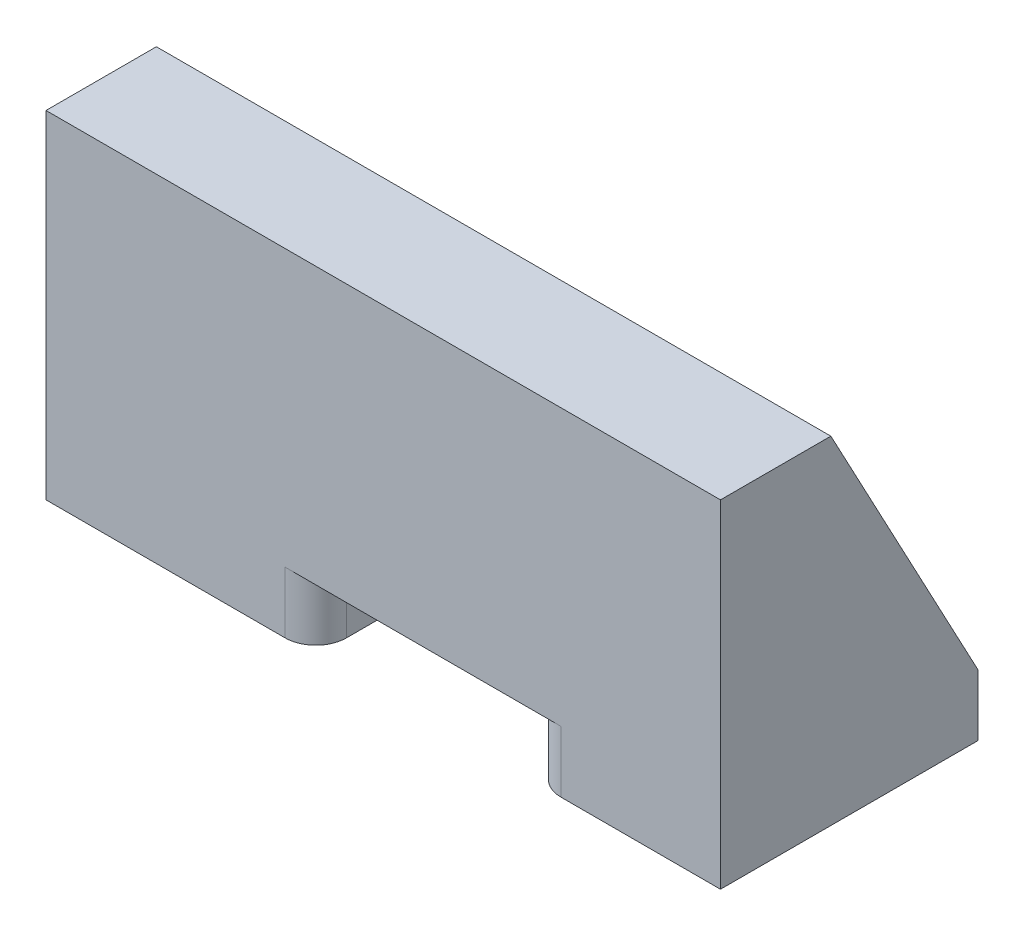
SolidWorks part; units mm, degrees
material "ABS"
ref_plane "Front" through (0, 0, 0) normal (0, 0, 1) x (1, 0, 0)
ref_plane "Top" through (0, 0, 0) normal (0, 1, 0) x (1, 0, 0)
ref_plane "Right" through (0, 0, 0) normal (1, 0, 0) x (0, 0, -1)
sketch "Sketch1" plane through (0, 0, 0) normal (0, 1, 0) x (1, 0, 0)
  line L1 (-55, -21) -> (55, -21)
  line L2 (-55, -21) -> (-55, 21)
  line L3 (-55, 21) -> (55, 21)
  line L4 (55, -21) -> (55, 21)
  line L5 (-55, -21) -> (55, 21) construction
  line L6 (-55, 21) -> (55, -21) construction
  point P0 (0, 0)
  dimension "D1" = 110
  dimension "D2" = 42
extrude "Boss-Extrude1" add sketch "Sketch1" along normal blind 10
hole_wizard "CBORE for M3 SBHCS1" positions "Sketch3" profile "Sketch2" counterbore size "M3" standard "ANSI Metric" end condition through all
sketch "Sketch3" plane through (0, 10, 0) normal (0, 1, 0) x (1, 0, 0)
  line L0 (-55, 8) -> (-45, 8) construction
  line L1 (-55, 21) -> (-55, -21) construction
  line L2 (-45, 8) -> (55, 8) construction
  line L3 (55, -21) -> (55, 21) construction
  line L5 (-55, -21) -> (55, -21) construction
  point P0 (-45, 8)
  point P2 (-32, 3)
  point P4 (32, 3)
  point P6 (45, 8)
  dimension "D1" = 90
  dimension "D2" = 29
  dimension "D3" = 13
  dimension "D4" = 5
  dimension "D5" = 13
  dimension "D6" = 5
  dimension "D7" = 10
sketch "Sketch2" plane through (-45, 10, -8) normal (1, 0, 0) x (0, 0, 1)
  line L0 (0, 0) -> (0, 10)
  line L1 (0, 10) -> (1.7, 10)
  line L3 (1.7, 10) -> (1.7, 5)
  line L4 (1.7, 5) -> (4, 5)
  line L5 (4, 5) -> (4, 0)
  line L7 (4, 0) -> (0, 0)
  line L11 (0, -6.35) -> (0, 107.95) construction
  dimension "Thru Hole Dia." = 3.4
  dimension "Thru Hole Depth" = 10
  dimension "C'Bore Dia." = 8
  dimension "C'Bore Depth" = 5
sketch "Sketch4" plane through (0, 10, 0) normal (0, 1, 0) x (1, 0, 0)
  line L3 (-55, -21) -> (55, -21) construction
  line L11 (24, -21) -> (24, 6)
  line L12 (19, 11) -> (-6, 11)
  line L13 (-11, 6) -> (-11, -21)
  line L14 (-11, -21) -> (24, -21)
  arc A0 (-6, 11) -> (-11, 6) centre (-6, 6) ccw
  arc A1 (19, 11) -> (24, 6) centre (19, 6) cw
  circle A2 centre (-32, 3) radius 1.7 construction
  point P11 (24, 11)
  dimension "D1" = 21
  dimension "D5" = 5
  dimension "D2" = 5
  dimension "D4" = 32
  dimension "D6" = 35
extrude "Cut-Extrude1" cut sketch "Sketch4" against normal up to surface (10 mm away) up to face at (-45, 0, -6.3)
fillet "Fillet2" radius 5 2 edges at (24, 5, 21) (-11, 5, 21)
sketch "Sketch6" plane through (0, 10, 0) normal (0, 1, 0) x (1, 0, 0)
  line L0 (55, -21) -> (55, 21) construction
  line L1 (-55, -21) -> (55, -21)
  line L2 (-55, -21) -> (-55, -3)
  line L3 (-55, -3) -> (55, -3)
  line L4 (55, -21) -> (55, -3)
  dimension "D1" = 18
extrude "Boss-Extrude2" add sketch "Sketch6" along normal blind 45
sketch "Sketch8" plane through (-55, 0, 0) normal (-1, 0, 0) x (0, 0, 1)
  line L0 (-21, 10) -> (3, 10)
  line L1 (3, 10) -> (3, 55)
  line L2 (3, 55) -> (-21, 10)
extrude "Boss-Extrude3" add sketch "Sketch8" against normal blind 5
sketch "Sketch9" plane through (55, 0, 0) normal (1, 0, 0) x (0, 0, -1)
  line L0 (-3, 10) -> (21, 10)
  line L1 (21, 10) -> (-3, 55)
  line L2 (-3, 55) -> (-3, 10)
extrude "Boss-Extrude4" add sketch "Sketch9" against normal blind 5
